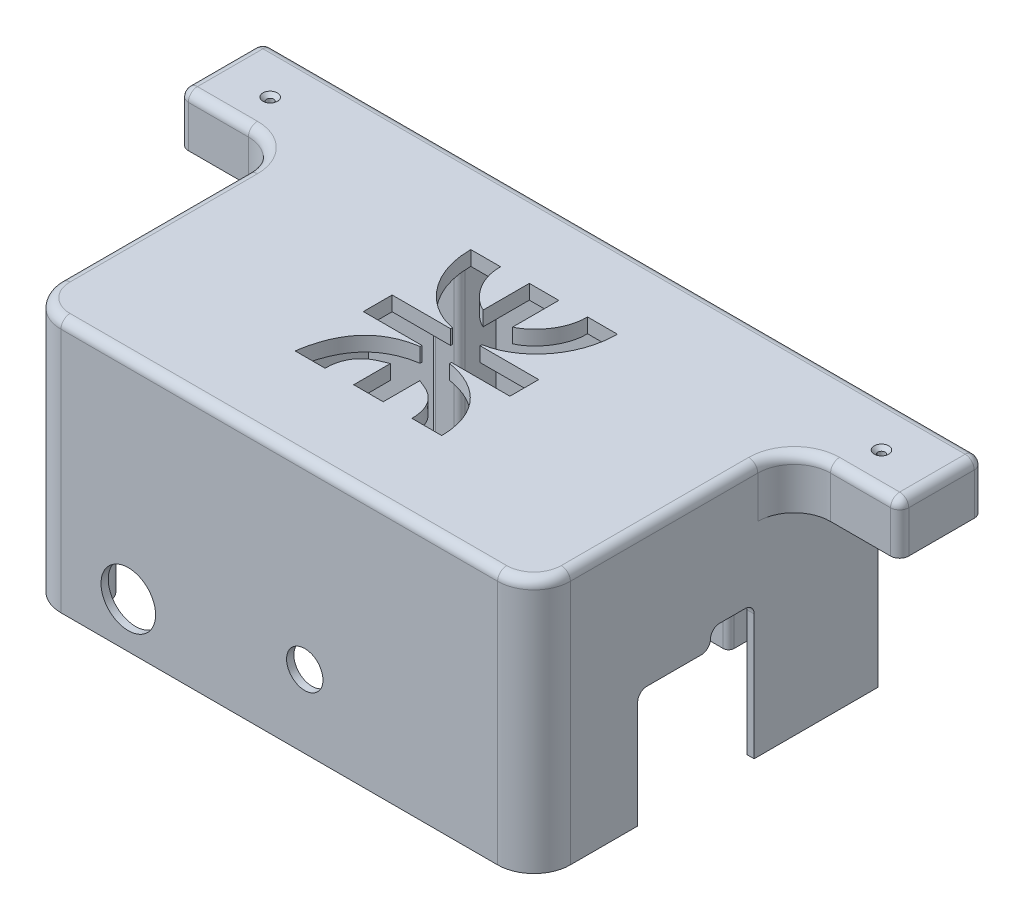
SolidWorks part; units mm, degrees
ref_plane "Alzado" through (0, 0, 0) normal (0, 0, 1) x (1, 0, 0)
ref_plane "Planta" through (0, 0, 0) normal (0, 1, 0) x (1, 0, 0)
ref_plane "Vista lateral" through (0, 0, 0) normal (1, 0, 0) x (0, 0, -1)
sketch "Croquis1" plane through (0, 0, 0) normal (0, 1, 0) x (1, 0, 0)
  line L0 (-70, -35.8212) -> (70, -35.8212)
  line L2 (-70, -35.8212) -> (-70, 35.6788)
  line L3 (-70, 35.6788) -> (-99, 35.6788)
  line L4 (-99, 35.6788) -> (-99, 58.6788)
  line L5 (0, -55) -> (0, 55) construction
  line L6 (99, 35.6788) -> (99, 58.6788)
  line L7 (70, 35.6788) -> (99, 35.6788)
  line L8 (70, -35.8212) -> (70, 35.6788)
  line L9 (-99, 58.6788) -> (99, 58.6788)
  point P6 (-70, -35.8212)
  point P7 (70, -35.8212)
extrude "Saliente-Extruir1" add sketch "Croquis1" along normal blind 70
sketch "Croquis2" plane through (0, 70, 0) normal (0, 1, 0) x (1, 0, 0)
  line L0 (-70, 35.6788) -> (-70, 58.6788)
  line L1 (99, 58.6788) -> (-99, 58.6788) construction
  line L2 (-70, 58.6788) -> (-99, 58.6788)
  line L3 (-99, 58.6788) -> (-99, 35.6788)
  line L4 (-99, 35.6788) -> (-70, 35.6788)
  line L5 (0, -38.5) -> (0, 38.5) construction
  line L6 (99, 58.6788) -> (99, 35.6788)
  line L7 (70, 58.6788) -> (99, 58.6788)
  line L8 (70, 35.6788) -> (70, 58.6788)
  line L9 (99, 35.6788) -> (70, 35.6788)
extrude "Cortar-Extruir1" cut sketch "Croquis2" along normal blind 56 from surface starting at plane "Planta"
sketch "Croquis3" plane through (0, 0, 0) normal (0, -1, 0) x (1, 0, 0)
  line L0 (-70, 35.8212) -> (-70, 33.8212) construction
  line L1 (-70, -58.6788) -> (-70, 35.8212) construction
  line L2 (-70, 35.8212) -> (-68, 35.8212) construction
  line L3 (-70, 35.8212) -> (70, 35.8212) construction
  line L4 (0, -38.5) -> (0, 38.5) construction
  line L5 (70, 35.8212) -> (68, 35.8212) construction
  line L6 (70, 35.8212) -> (70, 33.8212) construction
  line L7 (-70, -58.6788) -> (-70, -56.6788) construction
  line L8 (-70, -56.6788) -> (-68, -56.6788) construction
  line L9 (-68, 33.8212) -> (-68, -56.6788)
  line L10 (-68, -56.6788) -> (68, -56.6788)
  line L11 (68, -56.6788) -> (68, 33.8212)
  line L12 (68, 33.8212) -> (-68, 33.8212)
extrude "Cortar-Extruir2" cut sketch "Croquis3" against normal blind 66
fillet "Redondeo5" radius 10 2 edges at (70, 63, -35.6788) (-70, 63, -35.6788)
fillet "Redondeo13" radius 2.5 4 edges at (99, 63, -35.6788) (99, 63, -58.6788) (-99, 63, -58.6788) (-99, 63, -35.6788)
fillet "Redondeo14" radius 10 2 edges at (-68, 33, 33.8212) (68, 33, 33.8212)
fillet "Redondeo15" radius 10 2 edges at (70, 35, 35.8212) (-70, 35, 35.8212)
sketch "Croquis7" plane through (0, 0, -58.6788) normal (0, 0, -1) x (-1, 0, 0)
  line L0 (-7.5, 0) -> (7.5, 0)
  line L1 (51.975, 0) -> (-51.975, 0) construction
  line L2 (-7.5, 0) -> (-7.5, 13)
  line L3 (-7.5, 13) -> (7.5, 13)
  line L4 (7.5, 13) -> (7.5, 0)
  point P6 (0, 0)
  line M9 (-70, 0) -> (70, 0)
extrude "Cortar-Extruir4" cut sketch "Croquis7" against normal up to next from surface contours L4 L3 L2 M9 region at (0, 6.5, -58.6788) starting at face at (0, 45.5, -58.6788)
sketch "Croquis8" plane through (-70, 0, 0) normal (-1, 0, 0) x (0, 0, 1)
  line L0 (-58.6788, 0) -> (-24.6788, 0) construction
  line L1 (-58.6788, 0) -> (25.8212, 0) construction
  line L2 (-24.6788, 0) -> (-24.6788, 32)
  line L4 (7.3212, 32) -> (7.3212, 0)
  line L5 (7.3212, 0) -> (-24.6788, 0)
  line L6 (-24.6788, 32) -> (-24.6788, 37)
  line L7 (-24.6788, 37) -> (-12.6788, 37)
  line L8 (-12.6788, 37) -> (-12.6788, 32)
  line L9 (-12.6788, 32) -> (7.3212, 32)
extrude "Cortar-Extruir5" cut sketch "Croquis8" against normal up to surface (140 mm away) from surface up to face at (70, 42, -19.5121) starting at face at (-70, 42, -19.5121)
fillet "Redondeo16" radius 2.5 4 edges at (-69, 32, -12.6788) (-69, 32, 7.3212) (-69, 37, -24.6788) (-69, 37, -12.6788)
fillet "Redondeo17" radius 2.5 4 edges at (69, 37, -24.6788) (69, 37, -12.6788) (69, 32, -12.6788) (69, 32, 7.3212)
sketch "Croquis9" plane through (0, 0, 35.8212) normal (0, 0, 1) x (1, 0, 0)
  line L0 (-70, 2.1351) -> (-53, 2.1351) construction
  line L1 (-70, 0) -> (-70, 70) construction
  line L2 (-41.5, 5) -> (-41.5, 12.5) construction
  line L3 (-53, 0) -> (-53, 5) construction
  line L4 (51.975, 0) -> (-51.975, 0) construction
  line L5 (-53, 5) -> (-30, 5) construction
  line L6 (-70, 2.1351) -> (2, 2.1351) construction
  line L7 (2, 0) -> (2, 15) construction
  line L8 (2, 15) -> (12, 15) construction
  line L9 (12, 15) -> (12, 0) construction
  line L10 (7, 15) -> (7, 20) construction
  circle A0 centre (-41.5, 12.5) radius 7.5
  circle A1 centre (7, 20) radius 5
extrude "Cortar-Extruir6" cut sketch "Croquis9" against normal up to surface (2 mm away) up to face at (0, 33, 33.8212)
sketch "Croquis10" plane through (0, 0, 0) normal (0, 1, 0) x (1, 0, 0)
  line L0 (0, -38.5) -> (0, 38.5) construction
  line L1 (56, -21.8212) -> (68, -21.8212)
  line L2 (56, -33.8212) -> (56, -21.8212)
  line L6 (-56, -33.8212) -> (-56, -21.8212)
  line L8 (58, -33.8212) -> (-58, -33.8212) construction
  line L9 (-56, -21.8212) -> (-68, -21.8212)
  line L10 (-68, -23.8212) -> (-68, -7.3212) construction
  circle A0 centre (-62, -27.8212) radius 1
  arc A4 (-56, -33.8212) -> (-68, -21.8212) centre (-57.6744, -23.4956) cw
  circle A5 centre (62, -27.8212) radius 1
  arc A6 (56, -33.8212) -> (68, -21.8212) centre (57.6744, -23.4956) ccw
extrude "Saliente-Extruir8" add sketch "Croquis10" along normal up to surface (66 mm away) contours A4 L6 L9 A0 | A0 | L2 A6 L1 A5 | A5 region at (62, 0, 21.9928) region at (-64.9497, 0, 30.771) region at (-62, 0, 27.8212) region at (62, 0, 27.8212) up to face at (0, 66, 1.0116)
extrude "Cortar-Extruir7" cut sketch "Croquis10<4>" along normal blind 10 contours A5 | A0
sketch "Croquis10<4>" plane through (0, 0, 0) normal (0, 1, 0) x (1, 0, 0) same geometry as "Croquis10"
fillet "Redondeo18" radius 5 2 edges at (56, 33, 21.8212) (-56, 33, 21.8212)
sketch "Croquis12" plane through (0, 0, 0) normal (0, 1, 0) x (1, 0, 0)
  line L0 (-99, 58.6788) -> (-37, 58.6788) construction
  line L1 (-96.5, 58.6788) -> (-99, 58.6788) construction
  line L2 (-7.5, 58.6788) -> (-70, 58.6788) construction
  line L3 (-37, 58.6788) -> (-37, 50.6788) construction
  line L4 (-37, 56.6788) -> (-41, 56.6788) construction
  line L5 (-68, 56.6788) -> (68, 56.6788) construction
  line L6 (-41, 56.6788) -> (-41, 46.6788)
  line L7 (-41, 46.6788) -> (-32.997, 46.6788)
  line L8 (-32.997, 46.6788) -> (-32.997, 56.6788)
  line L9 (-68, 56.6788) -> (-7.5, 56.6788) construction
  line L10 (-32.997, 56.6788) -> (-41, 56.6788)
  line L11 (0, -38.5) -> (0, 38.5) construction
  line L12 (37, 56.6788) -> (41, 56.6788) construction
  line L13 (37, 58.6788) -> (37, 50.6788) construction
  line L14 (99, 58.6788) -> (37, 58.6788) construction
  line L15 (32.997, 56.6788) -> (41, 56.6788)
  line L16 (32.997, 46.6788) -> (32.997, 56.6788)
  line L17 (41, 46.6788) -> (32.997, 46.6788)
  line L18 (41, 56.6788) -> (41, 46.6788)
  circle A0 centre (-37, 50.6788) radius 1
  circle A1 centre (37, 50.6788) radius 1
extrude "Saliente-Extruir9" add sketch "Croquis12" along normal up to surface (66 mm away) contours L8 L10 L6 L7 A0 | A0 | L18 L15 L16 L17 A1 | A1 region at (-36.9984, 0, -51.7196) region at (36.9984, 0, -51.7196) region at (-37, 0, -50.6788) region at (37, 0, -50.6788) up to face at (0, 66, 9.3141)
extrude "Cortar-Extruir8" cut sketch "Croquis12<3>" along normal blind 10 contours A0 | A1
sketch "Croquis12<3>" plane through (0, 0, 0) normal (0, 1, 0) x (1, 0, 0) same geometry as "Croquis12"
fillet "Redondeo19" radius 1.5 4 edges at (-32.997, 33, -46.6788) (-41, 33, -46.6788) (32.997, 33, -46.6788) (41, 33, -46.6788)
sketch "Croquis13" plane through (0, 70, 0) normal (0, 1, 0) x (1, 0, 0)
  line L0 (-96.5, 35.6788) -> (-100.407, 35.6788) construction
  line L1 (-99, 38.1788) -> (-99, 35.6788) construction
  line L2 (-99, 35.6788) -> (-99, 45.6788) construction
  line L3 (-99, 56.1788) -> (-99, 38.1788) construction
  line L4 (-99, 45.6788) -> (-84, 45.6788) construction
  line L5 (0, -38.5) -> (0, 38.5) construction
  line L6 (99, 45.6788) -> (84, 45.6788) construction
  line L7 (99, 35.6788) -> (99, 45.6788) construction
  line L8 (99, 38.1788) -> (99, 35.6788) construction
  line L9 (96.5, 35.6788) -> (100.407, 35.6788) construction
  circle A0 centre (-84, 45.6788) radius 1
  circle A1 centre (84, 45.6788) radius 1
extrude "Cortar-Extruir9" cut sketch "Croquis13" against normal up to next
fillet "Redondeo20" radius 2.5 16 edges at (98.2678, 70, -57.9465) (99, 70, -47.1788) (98.2678, 70, -36.411) (88.25, 70, -35.6788) (72.9289, 70, -32.7498) (70, 70, 0.0712) (67.0711, 70, 32.8923) (0, 70, 35.8212) (-67.0711, 70, 32.8923) (-70, 70, 0.0712) (-72.9289, 70, -32.7498) (-88.25, 70, -35.6788) (-98.2678, 70, -36.411) (-99, 70, -47.1788) (-98.2678, 70, -57.9465) (0, 70, -58.6788)
chamfer "Chaflán1" distance 1 angle 45 2 edges at (84, 70, -46.6788) (-84, 70, -44.6788)
sketch "Croquis14" plane through (0, 70, 0) normal (0, 1, 0) x (1, 0, 0)
  line L0 (-20.1468, 15.0144) -> (20.1379, 15.0144) construction
  line L1 (-20.1468, 15.3402) -> (20.1379, 7.4225) construction
  line L2 (-20.1468, 36.9565) -> (-11.9507, 36.9565)
  line L3 (-4.0572, 36.9565) -> (-4.0572, 24.2899)
  line L4 (-4.0572, 36.9565) -> (-0.0045, 36.9565)
  line L5 (-4.0572, 15.8581) -> (-4.0572, 15.3402)
  line L6 (-4.0572, 15.3402) -> (-20.1468, 15.3402)
  line L7 (-20.1468, 15.3402) -> (-20.1468, 7.4225)
  line L8 (-20.1468, 7.4225) -> (-4.0572, 7.4225)
  line L9 (-4.0572, 7.4225) -> (-4.0572, 6.9139)
  line L10 (4.0521, -11.3155) -> (-4.0611, -11.3155)
  line L11 (-4.0611, -11.3155) -> (-4.0611, -1.2576)
  line L12 (-20.1468, -11.3155) -> (-12.2332, -11.3155)
  line L13 (-11.9507, -11.3155) -> (-12.2332, -11.3155)
  line L14 (4.0483, 7.4225) -> (4.0483, 6.9139)
  line L15 (4.0483, 15.8581) -> (4.0483, 15.3402)
  line L16 (4.0521, -11.3155) -> (4.0521, -1.2576)
  line L17 (20.1379, -11.3155) -> (12.2243, -11.3155)
  line L18 (20.1379, 7.4225) -> (4.0483, 7.4225)
  line L19 (20.1379, 15.3402) -> (20.1379, 7.4225)
  line L20 (4.0483, 15.3402) -> (20.1379, 15.3402)
  line L21 (20.1379, 36.9565) -> (11.9418, 36.9565)
  line L22 (4.0483, 36.9565) -> (4.0483, 24.2899)
  line L23 (4.0483, 36.9565) -> (-0.0045, 36.9565)
  line L24 (12.2243, -11.3155) -> (11.9418, -11.3155)
  line L25 (20.1379, 15.3402) -> (-20.1468, 7.4225) construction
  line L26 (0, 58.6788) -> (0, -35.9077) construction
  line L27 (-96.5, 58.6788) -> (96.5, 58.6788) construction
  line L28 (0, -38.5) -> (0, 38.5) construction
  spline S0 degree 3 poles (-20.1468, 36.9565) (-20.1986, 25.9232) (-12.5798, 17.333) (-4.0572, 15.8581) knots 0 0 0 0 1 1 1 1
  spline S1 degree 3 poles (-4.0572, 24.2899) (-6.6958, 25.2563) (-12.0748, 30.0997) (-11.9507, 36.9565) knots 0 0 0 0 1 1 1 1
  spline S2 degree 2 poles (-4.0572, 6.9139) (-17.8879, 4.7551) (-20.1468, -11.3155) knots 0 0 0 1 1 1
  spline S3 degree 3 poles (-4.0611, -1.2576) (-5.3686, -1.9436) (-11.8858, -3.0723) (-11.9507, -11.3155) knots 0 0 0 0 1 1 1 1
  spline S4 degree 3 poles (4.0521, -1.2576) (5.3597, -1.9436) (11.8768, -3.0723) (11.9418, -11.3155) knots 0 0 0 0 1 1 1 1
  spline S5 degree 3 poles (4.0483, 6.9139) (13.2688, 5.4747) (20.0634, -0.9824) (20.1379, -11.3155) knots 0 0 0 0 1 1 1 1
  spline S6 degree 3 poles (20.1379, 36.9565) (20.1897, 25.9232) (12.5709, 17.333) (4.0483, 15.8581) knots 0 0 0 0 1 1 1 1
  spline S7 degree 3 poles (4.0483, 24.2899) (6.6869, 25.2563) (12.0659, 30.0997) (11.9418, 36.9565) knots 0 0 0 0 1 1 1 1
  point P2 (-0.0045, 11.3814)
  point P28 (-0.0045, -11.3155)
  point P41 (0.0299, 15.0144)
extrude "Cortar-Extruir10" cut sketch "Croquis14" against normal up to next
